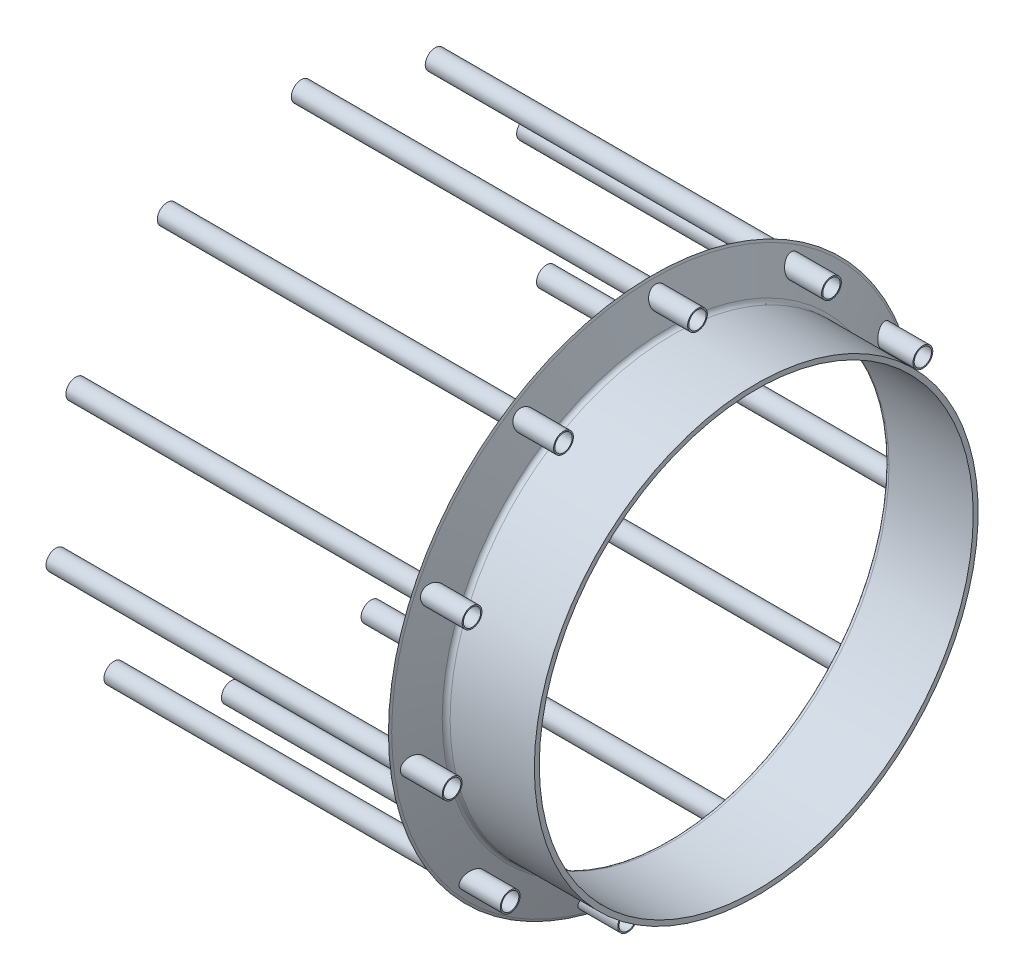
SolidWorks part; units mm, degrees
material "AISI 316 Stainless Steel Sheet (SS)"
ref_plane "Front Plane" through (0, 0, 0) normal (0, 0, 1) x (1, 0, 0)
ref_plane "Top Plane" through (0, 0, 0) normal (0, 1, 0) x (1, 0, 0)
ref_plane "Right Plane" through (0, 0, 0) normal (1, 0, 0) x (0, 0, -1)
sketch "Sketch1" plane through (0, 0, 0) normal (0, 0, 1) x (1, 0, 0)
  line L0 (-425.6547, -49.0203) -> (17637.5751, -49.0203) construction
  line L3 (40.0001, 3.4797) -> (40.0001, 4.4797)
  line L5 (40.0001, 3.4797) -> (42.9269, -4.5615)
  line L6 (43.8666, -4.2195) -> (60.8666, -4.2195)
  line L8 (40.0001, 3.4797) -> (40.0001, -0.5495) construction
  line L9 (43.8666, -5.2195) -> (60.8666, -5.2195)
  line L10 (60.8666, -4.2195) -> (60.8666, -5.2195)
  line L11 (40.0001, 4.4797) -> (42.9269, -3.5615)
  arc A0 (42.9269, -4.5615) -> (43.8666, -5.2195) centre (43.8666, -4.2195) ccw
  arc A1 (42.9269, -3.5615) -> (43.8666, -4.2195) centre (43.8666, -3.2195) ccw
  dimension "D4" = 1
  dimension "D1" = 53.5
  dimension "D2" = 1
  dimension "D3" = 1
  dimension "D5" = 17
revolve "Revolve1" add sketch "Sketch1" angle 360 about L0 region at (40.0231, 3.9797, 0)
fillet "Fillet1" radius 5 1 edges at (40.0001, -49.0203, 52.5)
fillet "Fillet2" radius 3 1 edges at (40.0001, -49.0203, 53.5)
ref_plane "Plane1" through (49, 0, 0) normal (1, 0, 0) x (0, 0, -1)
sketch "Sketch3" plane through (49, 0, 0) normal (1, 0, 0) x (0, 0, -1)
  circle A0 centre (0, 1) radius 2
  dimension "D2" = 4
  dimension "D1" = 1
extrude "Cut-Extrude1" cut sketch "Sketch3" against normal blind 10
sketch "Sketch6" plane through (0, 0, 0) normal (0, 0, 1) x (1, 0, 0)
  line L0 (-955.3214, -49.0203) -> (49044.6786, -49.0203) construction
  line L2 (60.8666, -4.2195) -> (43.8666, -4.2195) construction
  line L4 (60.8666, -92.8211) -> (60.8666, -5.2195) construction
  point P6 (60.8666, -49.0203)
pattern_circular "CirPattern1" count 11 over 360 about axis through (-955.3214, -49.0203, 0) along (1, 0, 0) of "Cut-Extrude1"
extrude "Boss-Extrude1" add sketch "Sketch3<2>" against normal blind 80
sketch "Sketch3<2>" plane through (49, 0, 0) normal (1, 0, 0) x (0, 0, -1) same geometry as "Sketch3"
pattern_circular "CirPattern2" count 11 over 360 about axis through (-955.3214, -49.0203, 0) along (1, 0, 0) of "Boss-Extrude1"
sketch "Sketch8" plane through (0, 0, 0) normal (0, 0, 1) x (1, 0, 0)
  circle A0 centre (57.5783, 0.9184) radius 2
  ellipse E0 centre (57.5783, 0.9184) end of major axis (57.5783, -2.3624) minor radius 3.0748
  dimension "D1" = 4
sketch "Sketch9" plane through (49, 0, 0) normal (1, 0, 0) x (0, 0, -1)
  circle A0 centre (0, 1) radius 1.75
  circle A1 centre (0, 1) radius 2 construction
  dimension "D1" = 3.5
extrude "Cut-Extrude2" cut sketch "Sketch9" against normal blind 90
pattern_circular "CirPattern3" count 11 over 360 about axis through (-955.3214, -49.0203, 0) along (1, 0, 0) of "Cut-Extrude2"
ref_plane "Plane2" through (55.8, 0, 0) normal (1, 0, 0) x (0, 0, -1)
sketch "Sketch10" plane through (55.8, 0, 0) normal (1, 0, 0) x (0, 0, -1)
  circle A0 centre (0, 1) radius 1
  circle A1 centre (0, 1) radius 1.75 construction
  circle A2 centre (0, 1) radius 0.7331
  dimension "D1" = 2
ref_plane "Plane3" through (0, -49.0203, 0) normal (0, 1, 0) x (1, 0, 0)
ref_plane "Plane4" through (0, 0, 70) normal (0, 0, 1) x (1, 0, 0)
sketch "Sketch11" plane through (0, 0, 70) normal (0, 0, 1) x (1, 0, 0)
  line L0 (-200955.3214, -49.0203) -> (249044.6786, -49.0203) construction
  line L1 (40.2062, -101.9542) -> (40.2062, 3.9136) construction
  circle A0 centre (57.9062, -49.0203) radius 2
  circle A1 centre (57.9062, -49.0203) radius 1.5
  dimension "D1" = 4
  dimension "D3" = 3
  dimension "D2" = 17.7
